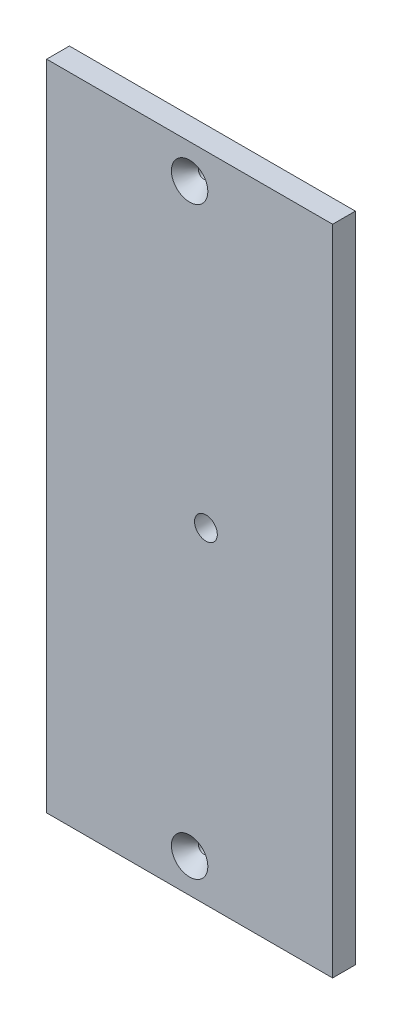
SolidWorks part; units mm, degrees
material "Beech"
ref_plane "Front Plane" through (0, 0, 0) normal (0, 0, 1) x (1, 0, 0)
ref_plane "Top Plane" through (0, 0, 0) normal (0, 1, 0) x (1, 0, 0)
ref_plane "Right Plane" through (0, 0, 0) normal (1, 0, 0) x (0, 0, -1)
sketch "Sketch1" plane through (0, 0, 0) normal (0, 0, 1) x (1, 0, 0)
  line L1 (-234.753, 19.05) -> (-314.5466, 19.05)
  line L2 (-234.753, 19.05) -> (-234.753, -163.1)
  line L3 (-234.753, -163.1) -> (-314.5466, -163.1)
  line L4 (-314.5466, 19.05) -> (-314.5466, -163.1)
  line L5 (-234.753, -163.1) -> (-350.6408, -163.1) construction
  dimension "D1" = 79.7937
extrude "Boss-Extrude1" add sketch "Sketch1" along normal blind 6.35 contours L4 L3 L2 L1
hole_wizard "1/4 (0.25) Diameter Hole1" positions "Sketch4" profile "Sketch5" hole size "1/4" standard "ANSI Inch" end condition through all
sketch "Sketch4" plane through (0, 0, 6.35) normal (0, 0, 1) x (1, 0, 0)
  point P0 (-270.0966, -72.025)
sketch "Sketch5" plane through (-270.0966, -72.025, 6.35) normal (1, 0, 0) x (0, -1, 0)
  line L0 (0, 0) -> (0, 6.35)
  line L1 (0, 6.35) -> (3.175, 6.35)
  line L2 (3.175, 6.35) -> (3.175, 0)
  line L5 (3.175, 0) -> (0, 0)
  line L11 (0, -6.35) -> (0, 107.95) construction
  dimension "Thru Hole Dia." = 6.35
  dimension "Thru Hole Depth" = 6.35
hole_wizard "Hole1" positions "Sketch6" profile "Sketch7" legacy
sketch "Sketch6" plane through (181.0394, -72.025, 6.35) normal (0, 0, 1) x (0, 1, 0)
  line L0 (91.075, 455.6892) -> (-91.075, 455.6892) construction
  point P0 (81.55, 455.6892)
  point P2 (-81.55, 455.6892)
sketch "Sketch7" plane through (-274.6498, 9.525, 6.35) normal (1, 0, 0) x (0, -1, 0)
  line L0 (0, 0) -> (0, 32.7039)
  line L1 (0, 32.7039) -> (1.5875, 31.75)
  line L2 (1.5875, 31.75) -> (1.5875, 4.0177)
  line L3 (1.5875, 4.0177) -> (5.08, 0)
  line L4 (5.08, 0) -> (0, 0)
  line L5 (0, -14.3089) -> (0, 102.4216) construction
  line L6 (0, 32.7039) -> (-1.5875, 31.75) construction
  line L7 (-1.5875, 4.0177) -> (-5.08, 0) construction
  dimension "Diameter" = 3.175
  dimension "Depth" = 31.75
  dimension "C-Sink Diameter" = 10.16
  dimension "C-Sink Angle" = 82
  dimension "Drill Angle" = 118
